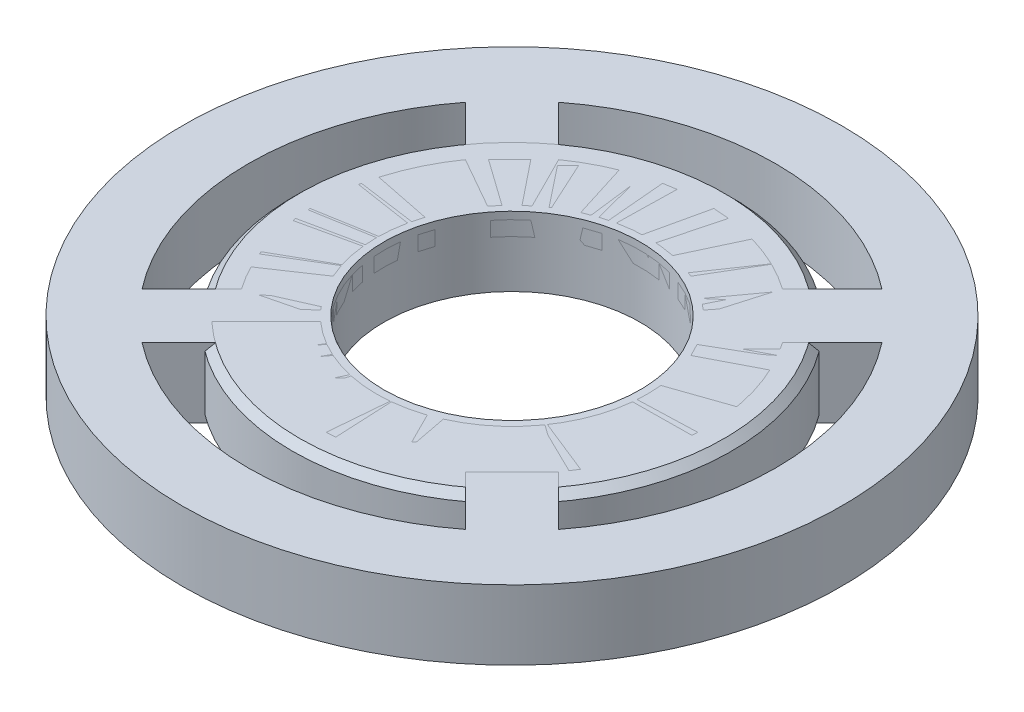
SolidWorks part; units mm, degrees
ref_plane "Front Plane" through (0, 0, 0) normal (0, 0, 1) x (1, 0, 0)
ref_plane "Top Plane" through (0, 0, 0) normal (0, 1, 0) x (1, 0, 0)
ref_plane "Right Plane" through (0, 0, 0) normal (1, 0, 0) x (0, 0, -1)
sketch "Sketch2" plane through (0, 0, 0) normal (0, 1, 0) x (1, 0, 0)
  line L0 (-45, 0) -> (45, 0) construction
  line L1 (-45, -45) -> (45, -45)
  line L2 (-45, -45) -> (-45, 45)
  line L3 (-45, 45) -> (45, 45)
  line L4 (45, -45) -> (45, 45)
  line L5 (-36, 0) -> (-45, 0) construction
  line L6 (36, 0) -> (45, 0) construction
  line L7 (-17.5, 0) -> (-26.5, 0) construction
  line L8 (-15.2842, 21.6482) -> (-22.0742, 28.4382)
  line L9 (-28.4382, 22.0742) -> (-21.6482, 15.2842)
  line L10 (15.2842, -21.6482) -> (22.0742, -28.4382)
  line L11 (21.6482, -15.2842) -> (28.4382, -22.0742)
  line L12 (-22.0742, -28.4382) -> (-15.2842, -21.6482)
  line L13 (-28.4382, -22.0742) -> (-21.6482, -15.2842)
  line L14 (15.2842, 21.6482) -> (22.0742, 28.4382)
  line L15 (21.6482, 15.2842) -> (28.4382, 22.0742)
  line L16 (-21.6482, -15.2842) -> (-15.2842, -21.6482) construction
  line L17 (-21.6482, 15.2842) -> (-15.2842, 21.6482) construction
  line L18 (-15.2842, -21.6482) -> (21.6482, 15.2842) construction
  line L19 (-21.6482, 15.2842) -> (15.2842, -21.6482) construction
  line L20 (0, -6.364) -> (0, 0)
  circle A0 centre (0, 0) radius 17.5
  circle A1 centre (0, 0) radius 45
  circle A2 centre (0, 0) radius 36
  circle A3 centre (0, 0) radius 26.5
  point P10 (0, 0)
  dimension "D1" = 35
  dimension "D2" = 9
  dimension "D3" = 90
  dimension "D4" = 9
  dimension "D5" = 9
extrude "Boss-Extrude2" add sketch "Sketch2" along normal blind 9.5 contours A1 A2 | A3 L15 A2 L14 | A3 L10 A2 L11 | A3 L13 A2 L12 | A3 L8 A2 L9 | A3 A0
sketch "Sketch4" plane through (0, 0, 0) normal (0, 1, 0) x (1, 0, 0)
  circle A0 centre (0, 0) radius 30
  circle A1 centre (0, 0) radius 17.5
  dimension "D1" = 60
  dimension "D2" = 35
extrude "Boss-Extrude3" add sketch "Sketch4" along normal blind 3 separate body
sketch "Sketch5" plane through (0, 3, 0) normal (0, 1, 0) x (1, 0, 0)
  line L0 (-25, 0) -> (-30, 0) construction
  circle A0 centre (0, 0) radius 30
  circle A1 centre (0, 0) radius 25
  circle A2 centre (0, 0) radius 30 construction
  circle A3 centre (0, 0) radius 17.5
  circle A4 centre (0, 0) radius 17.5 construction
  dimension "D1" = 5
extrude "Boss-Extrude4" add sketch "Sketch5" along normal blind 3.5
sketch "Sketch7" plane through (0, 6.5, 0) normal (0, 1, 0) x (1, 0, 0)
  circle A0 centre (0, 0) radius 30
  circle A1 centre (0, 0) radius 17.5
  point P3 (0, 0)
  point P4 (0, 0)
  dimension "D1" = 60
  dimension "D2" = 35
extrude "Boss-Extrude5" add sketch "Sketch7" along normal blind 3
chamfer "Chamfer1" distance 1 angle 45 1 edges at (0, 9.5, 30)
chamfer "Chamfer2" distance 1 angle 45 1 edges at (0, 0, 30)
chamfer "Chamfer3" distance 1 angle 45 1 edges at (0, 0, 17.5)
chamfer "Chamfer4" distance 1 angle 45 1 edges at (0, 9.5, 17.5)
